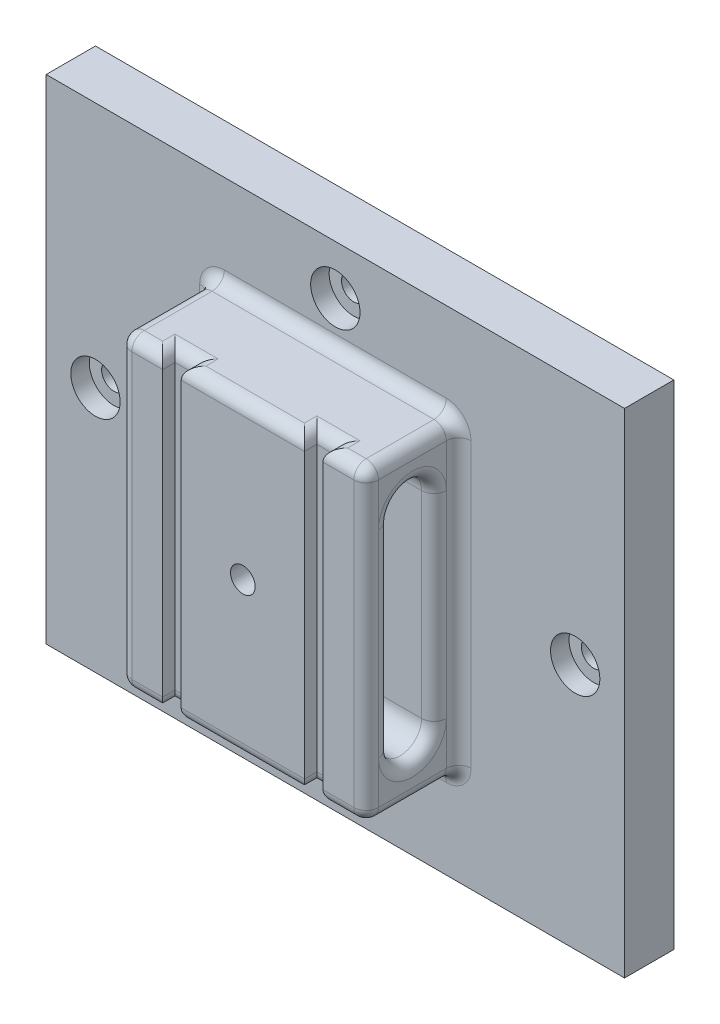
SolidWorks part; units mm, degrees
ref_plane "Front Plane" through (0, 0, 0) normal (0, 0, 1) x (1, 0, 0)
ref_plane "Top Plane" through (0, 0, 0) normal (0, 1, 0) x (1, 0, 0)
ref_plane "Right Plane" through (0, 0, 0) normal (1, 0, 0) x (0, 0, -1)
sketch "Sketch1" plane through (0, 0, 0) normal (0, 0, 1) x (1, 0, 0)
  line L1 (-46.9, -40) -> (46.9, -40)
  line L2 (-46.9, -40) -> (-46.9, 40)
  line L3 (-46.9, 40) -> (46.9, 40)
  line L4 (46.9, -40) -> (46.9, 40)
  line L5 (-46.9, -40) -> (46.9, 40) construction
  line L6 (-46.9, 40) -> (46.9, -40) construction
  point P0 (0, 0)
  dimension "D1" = 93.8
  dimension "D2" = 80
extrude "Boss-Extrude1" add sketch "Sketch1" along normal blind 8
sketch "Sketch2" plane through (0, 0, 8) normal (0, 0, 1) x (1, 0, 0)
  line L0 (-46.9, 0) -> (46.9, 0) construction
  line L1 (-46.9, 40) -> (-46.9, -40) construction
  line L2 (46.9, -40) -> (46.9, 40) construction
  line L4 (-20, -25) -> (20, -25)
  line L5 (-20, -25) -> (-20, 25)
  line L6 (-20, 25) -> (20, 25)
  line L7 (20, -25) -> (20, 25)
  line L8 (-20, -25) -> (20, 25) construction
  line L9 (-20, 25) -> (20, -25) construction
  point P6 (0, 0)
  dimension "D1" = 40
  dimension "D2" = 50
extrude "Boss-Extrude2" add sketch "Sketch2" along normal blind 15
sketch "Sketch4" plane through (0, 0, 0) normal (0, 0, -1) x (-1, 0, 0)
  circle A0 centre (0, -32) radius 2
  circle A1 centre (0, 32) radius 2
  circle A2 centre (38.9, 0) radius 2
  circle A3 centre (-38.9, 0) radius 2
extrude "Cut-Extrude2" cut sketch "Sketch4" against normal through all
sketch "Sketch5" plane through (0, 0, 0) normal (0, 0, -1) x (-1, 0, 0)
  line L1 (0, 4.001) -> (-3.465, 2.0005)
  line L2 (-3.465, 2.0005) -> (-3.465, -2.0005)
  line L3 (-3.465, -2.0005) -> (0, -4.001)
  line L4 (0, -4.001) -> (3.465, -2.0005)
  line L5 (3.465, -2.0005) -> (3.465, 2.0005)
  line L6 (3.465, 2.0005) -> (0, 4.001)
  circle A0 centre (0, 0) radius 3.465 construction
  dimension "D1" = 6.93
extrude "Cut-Extrude3" cut sketch "Sketch5" against normal blind 5
sketch "Sketch7" plane through (0, 0, 5) normal (0, 0, -1) x (-1, 0, 0)
  circle A0 centre (0, 0) radius 2
extrude "Cut-Extrude4" cut sketch "Sketch7" against normal blind 20
sketch "Sketch8" plane through (0, 0, 8) normal (0, 0, 1) x (1, 0, 0)
  circle A0 centre (0, 32) radius 4
  circle A1 centre (38.9, 0) radius 4
  circle A2 centre (0, -32) radius 4
  circle A3 centre (-38.9, 0) radius 4
  dimension "D1" = 8
extrude "Cut-Extrude5" cut sketch "Sketch8" against normal blind 3
sketch "Sketch9" plane through (20, 0, 0) normal (1, 0, 0) x (0, 0, -1)
  line L0 (-15.5, 25) -> (-15.5, -25) construction
  line L1 (-23, 25) -> (-8, 25) construction
  line L2 (-23, -25) -> (-8, -25) construction
  line L3 (-15.5, 16) -> (-15.5, -16) construction
  line L4 (-12, 16) -> (-12, -16)
  line L5 (-19, 16) -> (-19, -16)
  arc A0 (-12, 16) -> (-19, 16) centre (-15.5, 16) ccw
  arc A1 (-19, -16) -> (-12, -16) centre (-15.5, -16) ccw
  point P8 (-15.5, 0)
  dimension "D2" = 3.5
  dimension "D1" = 32
extrude "Cut-Extrude6" cut sketch "Sketch9" against normal through all
sketch "Sketch10" plane through (0, 0, 23) normal (0, 0, 1) x (1, 0, 0)
  line L0 (20, 25) -> (-20, 25) construction
  line L1 (-13, 25) -> (-10, 25)
  line L2 (-13, 25) -> (-13, -25)
  line L3 (-13, -25) -> (-10, -25)
  line L4 (-10, 25) -> (-10, -25)
  line L5 (-20, -25) -> (20, -25) construction
  line L6 (0, 25) -> (0, 0) construction
  line L7 (10, 25) -> (10, -25)
  line L8 (13, -25) -> (10, -25)
  line L9 (13, 25) -> (13, -25)
  line L10 (13, 25) -> (10, 25)
  dimension "D1" = 3
  dimension "D2" = 10
extrude "Cut-Extrude7" cut sketch "Sketch10" against normal blind 2
fillet "Fillet2" radius 2 36 edges at (20, 0, 23) (20, 0, 8) (20, -19.5, 15.5) (20, 0, 12) (20, 19.5, 15.5) (20, 0, 19) (0, 25, 8) (20, 25, 15.5) (16.5, 25, 23) (13, 25, 22) (11.5, 25, 21) (10, 25, 22) (0, 25, 23) (-10, 25, 22) (-11.5, 25, 21) (-13, 25, 22) (-16.5, 25, 23) (-20, 25, 15.5) (-20, 0, 23) (-20, 0, 8) (-20, -19.5, 15.5) (-20, 0, 19) (-20, 19.5, 15.5) (-20, 0, 12) (-10, -25, 22) (0, -25, 23) (10, -25, 22) (11.5, -25, 21) (13, -25, 22) (16.5, -25, 23) (20, -25, 15.5) (0, -25, 8) (-20, -25, 15.5) (-16.5, -25, 23) (-13, -25, 22) (-11.5, -25, 21)
